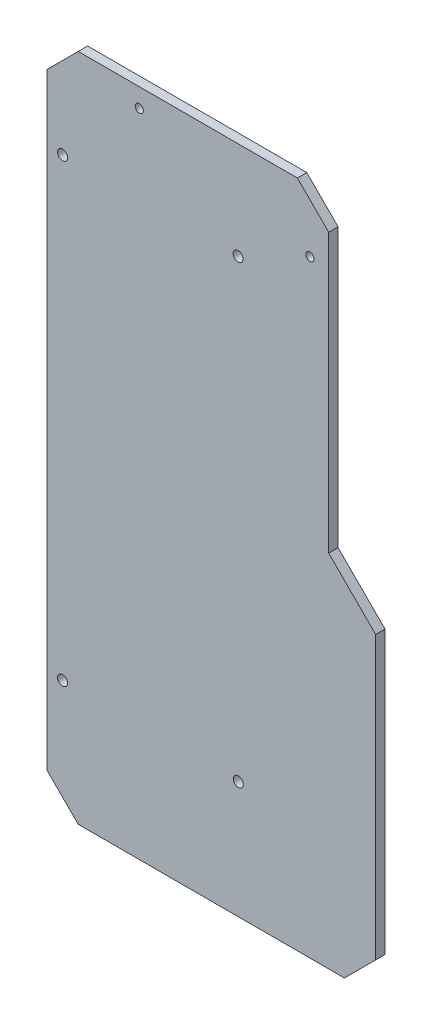
SolidWorks part; units mm, degrees
ref_plane "Front Plane" through (0, 0, 0) normal (0, 0, 1) x (1, 0, 0)
ref_plane "Top Plane" through (0, 0, 0) normal (0, 1, 0) x (1, 0, 0)
ref_plane "Right Plane" through (0, 0, 0) normal (1, 0, 0) x (0, 0, -1)
sketch "Sketch1" plane through (0, 0, 0) normal (0, 0, 1) x (1, 0, 0)
  line L0 (-80, -0.7565) -> (-80, 4.2435) construction
  line L1 (-70, 34.0035) -> (0, 34.0035)
  line L2 (-80, 24.0035) -> (-80, -169.754)
  line L3 (-70, -179.754) -> (0, -179.754)
  line L6 (-14, -149.754) -> (-80, -149.754) construction
  line L8 (10, -64.754) -> (10, 24.0035)
  line L9 (-80, 24.0035) -> (-70, 34.0035)
  line L10 (10, 24.0035) -> (0, 34.0035)
  line L11 (-80, -169.754) -> (-70, -179.754)
  line L13 (10, -64.754) -> (25, -79.754)
  line L14 (25, -79.754) -> (25, -169.754)
  line L15 (15, -179.754) -> (0, -179.754)
  line L16 (25, -169.754) -> (15, -179.754)
  line L17 (-80, 10.2435) -> (-14, 10.2435) construction
  circle A0 centre (-75, 2.8935) radius 1.6
  circle A1 centre (-18.9466, 2.8935) radius 1.6
  circle A2 centre (-75, -142.404) radius 1.6
  circle A3 centre (-18.8932, -142.404) radius 1.6
  circle A6 centre (4, 14.2435) radius 1.3
  circle A7 centre (-50.5, 28.0035) radius 1.3
  point P0 (-80, 34.0035)
  point P2 (-80, -179.754)
  point P12 (10, 34.0035)
  point P32 (25, -179.754)
  dimension "D2" = 3.2
  dimension "D1" = 30
  dimension "D3" = 90
  dimension "D4" = 45
  dimension "D6" = 23.76
  dimension "D7" = 100
  dimension "D10" = 15
extrude "Extrude1" add sketch "Sketch1" along normal blind 3
